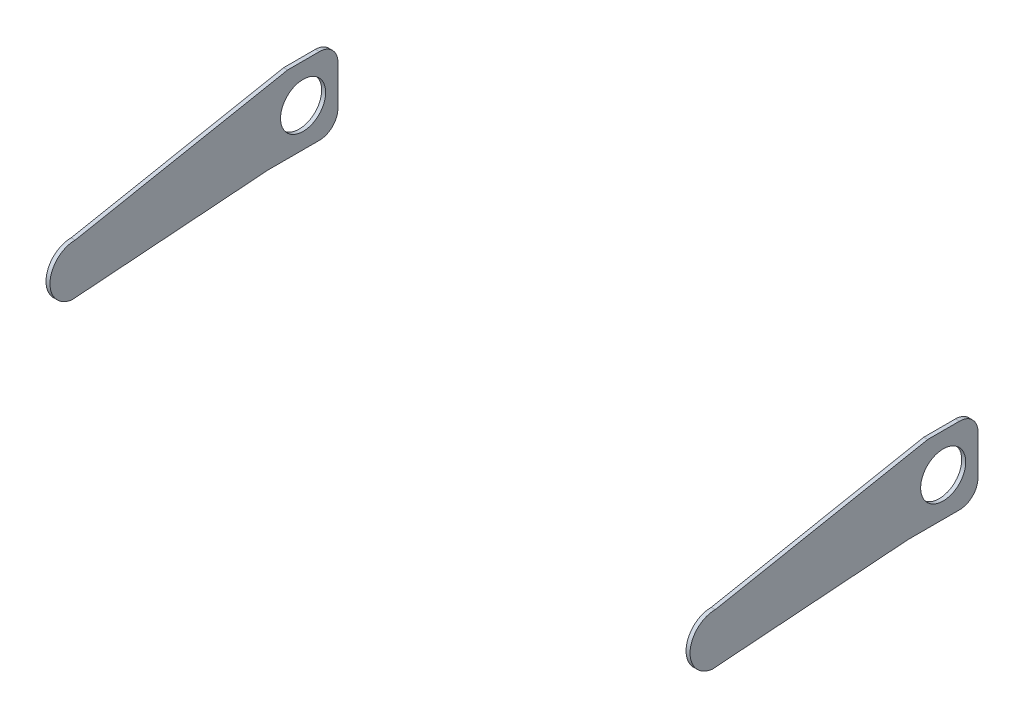
SolidWorks part; units mm, degrees
ref_plane "Front Plane" through (0, 0, 0) normal (0, 0, 1) x (1, 0, 0)
ref_plane "Top Plane" through (0, 0, 0) normal (0, 1, 0) x (1, 0, 0)
ref_plane "Right Plane" through (0, 0, 0) normal (1, 0, 0) x (0, 0, -1)
ref_plane "Plane2" through (-120, 0, 0) normal (-1, 0, 0) x (0, 0, 1)
sketch "Sketch1" plane through (-120, 0, 0) normal (-1, 0, 0) x (0, 0, 1)
  line L0 (-8.5, -10.5) -> (30.5, -10.5) construction
  line L1 (12.1276, -19.9328) -> (-61.8571, -14.5)
  line L8 (-69.1429, 14.5) -> (11, -1)
  line L9 (-100, -15) -> (-50, -15) construction
  line L10 (-61.8571, -14.5) -> (-81.1429, -14.5)
  line L12 (-69.1429, 14.5) -> (-81.1429, 14.5)
  line L13 (-88.1429, -7.5) -> (-88.1429, 7.5)
  line L14 (-61.8571, -14.5) -> (-88.1429, 14.5) construction
  line L15 (-62.9438, 13.3011) -> (-88.1429, -14.5) construction
  line L16 (-100, 24) -> (-100, -15) construction
  arc A1 (12.1276, -19.9328) -> (11, -1) centre (11, -10.5) ccw
  circle A3 centre (-75, 0) radius 8.5
  circle A5 centre (11, -10.5) radius 8.5 construction
  arc A6 (-81.1429, 14.5) -> (-88.1429, 7.5) centre (-81.1429, 7.5) ccw
  arc A7 (-81.1429, -14.5) -> (-88.1429, -7.5) centre (-81.1429, -7.5) cw
  dimension "D1" = 19
  dimension "D2" = 7
  dimension "D3" = 17
  dimension "D5" = 17
  dimension "D4" = 7
  dimension "D6" = 29
  dimension "D7" = 0.5
  dimension "D8" = 12
  dimension "D9" = 11.8571
extrude "Boss-Extrude1" add sketch "Sketch1" along normal blind 1.5
mirror "Mirror2" about plane through (0, 0, 0) normal (1, 0, 0) of bodies 101
